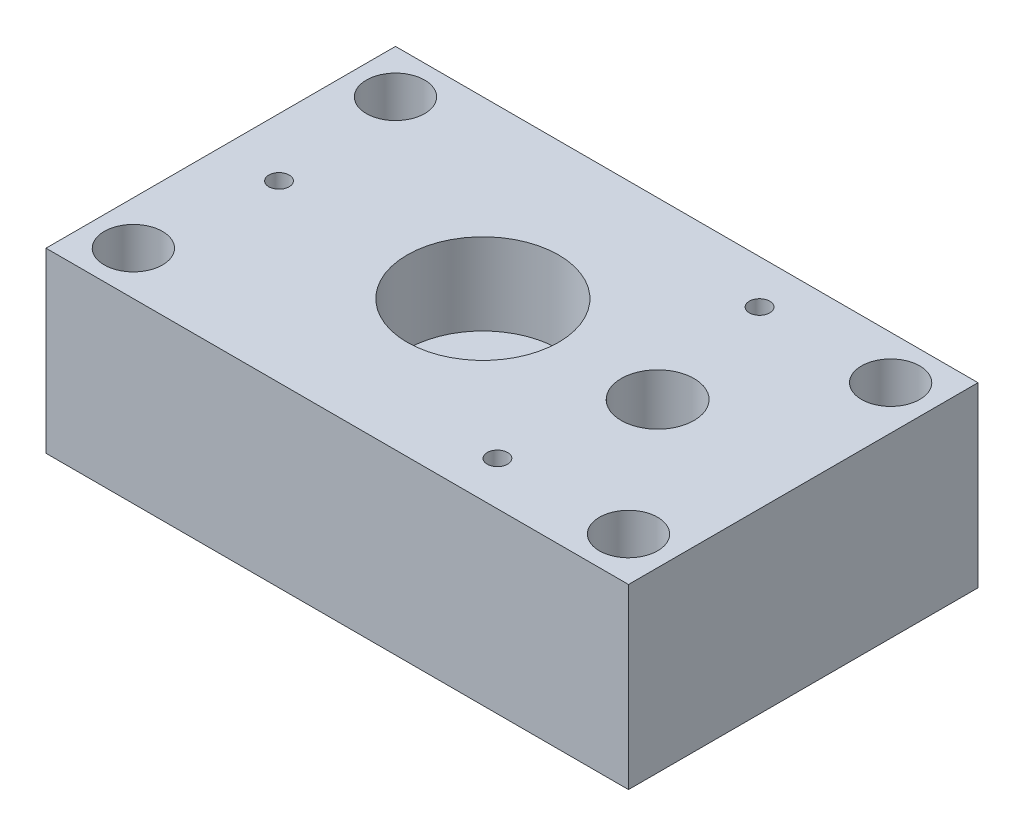
SolidWorks part; units mm, degrees
ref_plane "前视基准面" through (0, 0, 0) normal (0, 0, 1) x (1, 0, 0)
ref_plane "上视基准面" through (0, 0, 0) normal (0, 1, 0) x (1, 0, 0)
ref_plane "右视基准面" through (0, 0, 0) normal (1, 0, 0) x (0, 0, -1)
other "Configuration Table"
sketch "草图1" plane through (0, 0, 0) normal (0, 1, 0) x (1, 0, 0)
  line L1 (0, 0) -> (20, 0)
  line L2 (0, 0) -> (0, -12)
  line L3 (0, -12) -> (20, -12)
  line L4 (20, 0) -> (20, -12)
  circle A4 centre (15, -6) radius 1.25
  circle A6 centre (7.6787, -8.9706) radius 0.6
  circle A8 centre (9.8471, -3.8074) radius 2.6
  circle A9 centre (9, -6) radius 2.6
  circle A10 centre (9, -6) radius 5
  circle A11 centre (15, -6) radius 3
  point P10 (0, 0)
  dimension "D2" = 5.2
  dimension "D3" = 5.6
  dimension "D6" = 10
  dimension "D4" = 20
  dimension "D5" = 2.5
  dimension "D7" = 6
  dimension "D14" = 1.2
  dimension "D15" = 5.2
  dimension "D8" = 6
  dimension "D11" = 12
  dimension "D12" = 5.6
extrude "凸台-拉伸1" add sketch "草图1" along normal blind 2.8 contours L1 L4 L3 L2 | A4 | A8 | A6
extrude "凸台-拉伸2" add sketch "草图1<9>" along normal blind 0.5 from surface contours L2 L3 L4 L1 | A4 starting at face at (9.8471, 2.8, 6.4074)
sketch "草图1<9>" plane through (0, 0, 0) normal (0, 1, 0) x (1, 0, 0) same geometry as "草图1"
extrude "凸台-拉伸3" add sketch "草图1<10>" along normal blind 2.8 from surface contours L1 L4 L3 L2 | A9 | A4 starting at face at (10, 3.3, 6)
sketch "草图1<10>" plane through (0, 0, 0) normal (0, 1, 0) x (1, 0, 0) same geometry as "草图1"
sketch "草图3" plane through (0, 0, 0) normal (0, 1, 0) x (1, 0, 0)
  circle A0 centre (1.5, -1.5) radius 0.75
  circle A1 centre (1.5, -10.5) radius 0.75
  circle A2 centre (18.5, -10.5) radius 0.75
  circle A3 centre (18.5, -1.5) radius 0.75
  circle A4 centre (1.5, -1.5) radius 1
  circle A5 centre (1.5, -10.5) radius 1
  circle A6 centre (18.5, -1.5) radius 1
  circle A7 centre (18.5, -10.5) radius 1
  circle A8 centre (2, -6) radius 0.35
  circle A9 centre (14, -1.5) radius 0.35
  circle A10 centre (14, -10.5) radius 0.35
  dimension "D1" = 2
  dimension "D2" = 1.5
  dimension "D3" = 0.7
extrude "切除-拉伸3" cut sketch "草图3" along normal through all contours A0 | A1 | A3 | A2 | A8 | A9 | A10
extrude "切除-拉伸5" cut sketch "草图3<4>" against normal offset from surface (5.1 mm away) 1 from surface contours A6 | A7 | A5 | A4 up to face at (2, 0, 6.35) starting at face at (2, 6.1, 6.35)
sketch "草图3<4>" plane through (0, 0, 0) normal (0, 1, 0) x (1, 0, 0) same geometry as "草图3"
